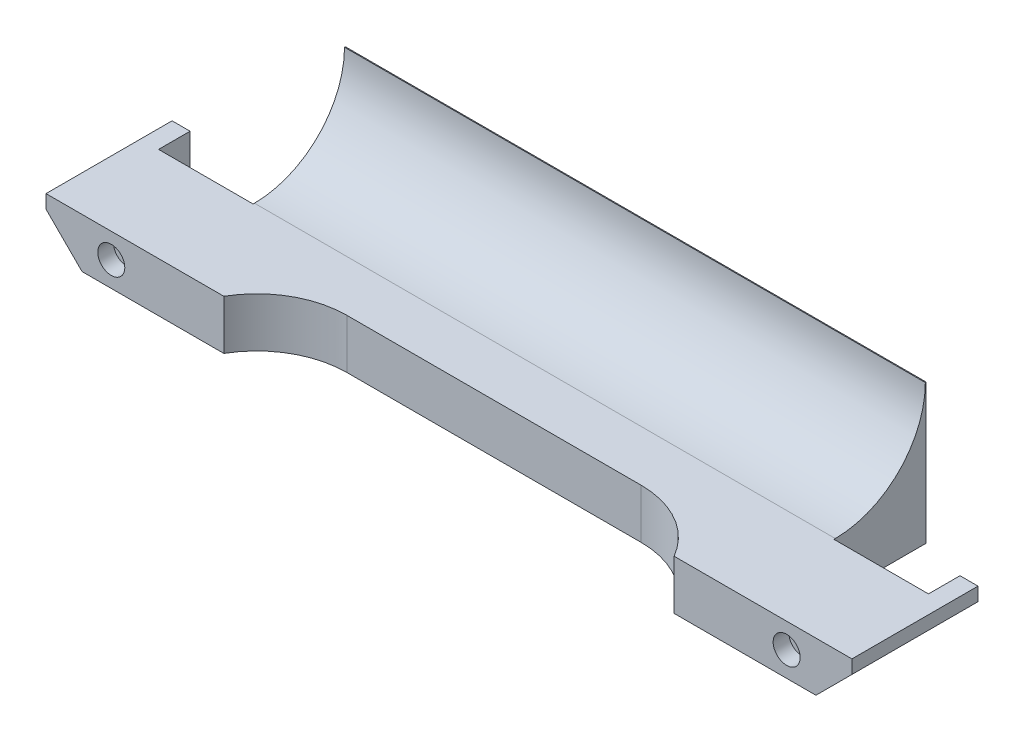
SolidWorks part; units mm, degrees
ref_plane "Top Plane" through (0, 0, 0) normal (0, 0, 1) x (1, 0, 0)
ref_plane "Front Plane" through (0, 0, 0) normal (0, 1, 0) x (1, 0, 0)
ref_plane "Right Plane" through (0, 0, 0) normal (1, 0, 0) x (0, 0, -1)
sketch "Sketch1" plane through (0, 0, 0) normal (0, 0, 1) x (1, 0, 0)
  line L1 (-64.5, -11.5) -> (64.5, -11.5)
  line L2 (-64.5, -11.5) -> (-64.5, 11.5)
  line L3 (-64.5, 11.5) -> (64.5, 11.5)
  line L4 (64.5, -11.5) -> (64.5, 11.5)
  line L5 (-64.5, -11.5) -> (64.5, 11.5) construction
  line L6 (-64.5, 11.5) -> (64.5, -11.5) construction
  point P0 (0, 0)
  dimension "D1" = 129
  dimension "D2" = 23
extrude "Boss-Extrude1" add sketch "Sketch1" along normal blind 0.2
sketch "Sketch2" plane through (0, 0, 0.2) normal (0, 0, 1) x (1, 0, 0)
  line L0 (64.5, -11.5) -> (64.5, 11.5) construction
  line L1 (-64.5, -11.5) -> (64.5, -11.5)
  line L2 (-64.5, -11.5) -> (-64.5, -8.5)
  line L3 (-64.5, -8.5) -> (64.5, -8.5)
  line L4 (64.5, -11.5) -> (64.5, -8.5)
  dimension "D1" = 3
extrude "Boss-Extrude2" add sketch "Sketch2" along normal blind 20.3
fillet "Fillet1" radius 20 1 edges at (0, -8.5, 0.2)
sketch "Sketch3" plane through (0, 0, 20.5) normal (0, 0, 1) x (1, 0, 0)
  line L0 (-64.5, -11.5) -> (64.5, -11.5) construction
  line L1 (-89.5, -8.5) -> (89.5, -8.5)
  line L2 (-89.5, -8.5) -> (-89.5, -11.5)
  line L3 (-89.5, -11.5) -> (89.5, -11.5)
  line L4 (89.5, -8.5) -> (89.5, -11.5)
  line L5 (-89.5, -8.5) -> (89.5, -11.5) construction
  line L6 (-89.5, -11.5) -> (89.5, -8.5) construction
  point P0 (0, -10)
  dimension "D1" = 179
  dimension "D2" = 3
  dimension "D3" = 0
  dimension "D4" = 0
extrude "Boss-Extrude3" add sketch "Sketch3" along normal blind 21
sketch "Sketch4" plane through (0, -11.5, 0) normal (0, -1, 0) x (1, 0, 0)
  line L1 (-89.5, 20.5) -> (-85.5, 20.5)
  line L2 (-89.5, 20.5) -> (-89.5, 13.5)
  line L3 (-89.5, 13.5) -> (-85.5, 13.5)
  line L4 (-85.5, 20.5) -> (-85.5, 13.5)
  line L5 (89.5, 20.5) -> (85.5, 20.5)
  line L6 (89.5, 20.5) -> (89.5, 13.5)
  line L7 (89.5, 13.5) -> (85.5, 13.5)
  line L8 (85.5, 20.5) -> (85.5, 13.5)
  dimension "D1" = 7
  dimension "D2" = 4
  dimension "D3" = 7
  dimension "D4" = 4
extrude "Boss-Extrude4" add sketch "Sketch4" against normal blind 3
sketch "Sketch5" plane through (0, -11.5, 0) normal (0, -1, 0) x (1, 0, 0)
  line L24 (-64.5, 0) -> (64.5, 0)
  line L25 (64.5, 0) -> (64.5, 20.5)
  line L26 (64.5, 20.5) -> (85.5, 20.5)
  line L27 (85.5, 20.5) -> (85.5, 13.5)
  line L28 (85.5, 13.5) -> (89.5, 13.5)
  line L29 (89.5, 13.5) -> (89.5, 41.5)
  line L30 (89.5, 41.5) -> (-89.5, 41.5)
  line L31 (-89.5, 41.5) -> (-89.5, 13.5)
  line L32 (-89.5, 13.5) -> (-85.5, 13.5)
  line L33 (-85.5, 13.5) -> (-85.5, 20.5)
  line L34 (-85.5, 20.5) -> (-64.5, 20.5)
  line L35 (-64.5, 20.5) -> (-64.5, 0)
  line L36 (-64.5, 0) -> (64.5, 0)
  line L37 (64.5, 0) -> (64.5, 20.5)
  line L38 (64.5, 20.5) -> (85.5, 20.5)
  line L39 (85.5, 20.5) -> (85.5, 13.5)
  line L40 (85.5, 13.5) -> (89.5, 13.5)
  line L41 (89.5, 13.5) -> (89.5, 41.5)
  line L42 (89.5, 41.5) -> (-89.5, 41.5)
  line L43 (-89.5, 41.5) -> (-89.5, 13.5)
  line L44 (-89.5, 13.5) -> (-85.5, 13.5)
  line L45 (-85.5, 13.5) -> (-85.5, 20.5)
  line L46 (-85.5, 20.5) -> (-64.5, 20.5)
  line L47 (-64.5, 20.5) -> (-64.5, 0)
  dimension "D1" = 0
extrude "Boss-Extrude5" add sketch "Sketch5" along normal blind 8
chamfer "Chamfer1" distance 8 angle 45 2 edges at (89.5, -19.5, 27.5) (-89.5, -19.5, 27.5)
sketch "Sketch6" plane through (0, 0, 41.5) normal (0, 0, 1) x (1, 0, 0)
  line L2 (81.5, -19.5) -> (-81.5, -19.5) construction
  circle A0 centre (-75, -14) radius 1.75
  circle A1 centre (75, -14) radius 1.75
  dimension "D2" = 75
  dimension "D3" = 5.5
  dimension "D4" = 5.5
  dimension "D5" = 3.5
  dimension "D6" = 3.5
  dimension "D1" = 150
extrude "screw holes" cut sketch "Sketch6" against normal through all
sketch "Sketch8" plane through (0, 0, 41.5) normal (0, 0, 1) x (1, 0, 0)
  circle A0 centre (-75, -14) radius 3
  circle A1 centre (75, -14) radius 3
  dimension "D1" = 6
  dimension "D2" = 6
extrude "screw headsinks" cut sketch "Sketch8" against normal blind 3.5
sketch "Sketch7" plane through (0, 0, 41.5) normal (0, 0, 1) x (1, 0, 0)
  line L0 (89.5, -8.5) -> (-89.5, -8.5) construction
  line L1 (-50, -8.5) -> (50, -8.5)
  line L2 (-50, -8.5) -> (-50, -19.5)
  line L3 (-50, -19.5) -> (50, -19.5)
  line L4 (50, -8.5) -> (50, -19.5)
  line L5 (81.5, -19.5) -> (-81.5, -19.5) construction
  dimension "D1" = 100
  dimension "D2" = 50
extrude "Cut-Extrude2" cut sketch "Sketch7" against normal blind 10
fillet "Fillet2" radius 20 2 edges at (50, -14, 31.5) (-50, -14, 31.5)
